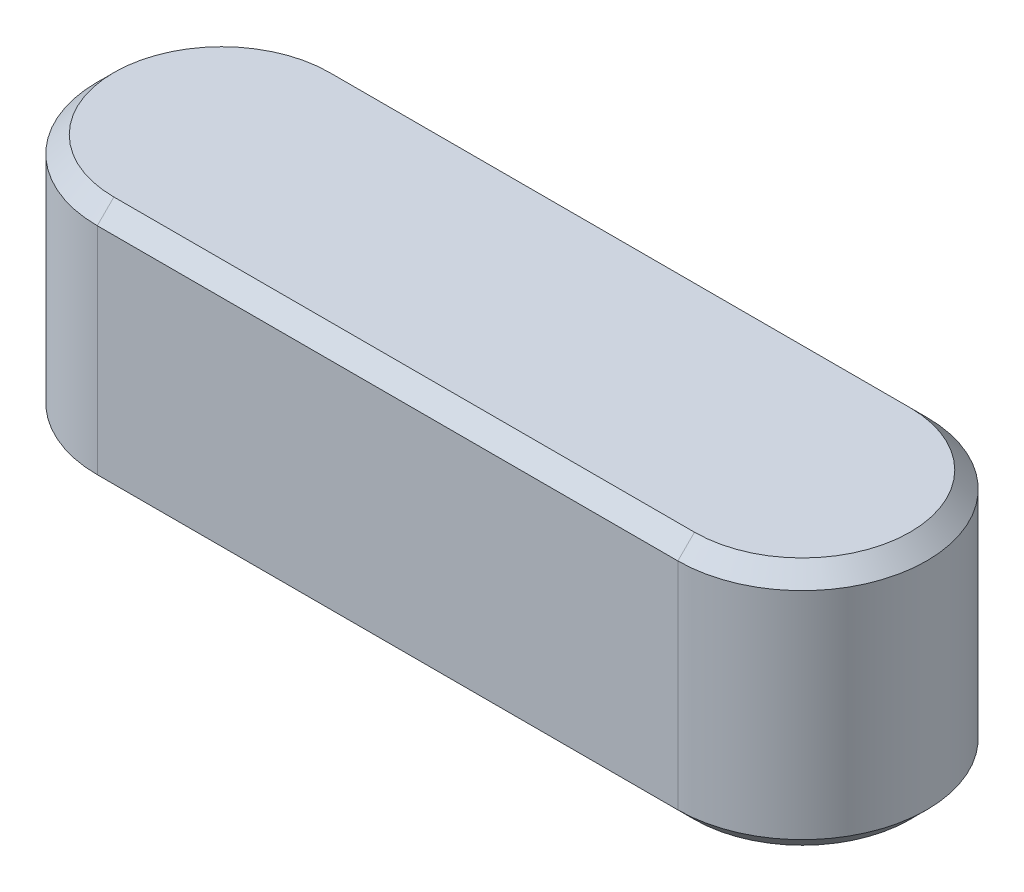
SolidWorks part; units mm, degrees
material "S45C"
ref_plane "Front Plane" through (0, 0, 0) normal (0, 0, 1) x (1, 0, 0)
ref_plane "Top Plane" through (0, 0, 0) normal (0, 1, 0) x (1, 0, 0)
ref_plane "Right Plane" through (0, 0, 0) normal (1, 0, 0) x (0, 0, -1)
sketch "Sketch1" plane through (0, 0, 0) normal (0, 1, 0) x (1, 0, 0)
  line L0 (-5, 0) -> (5, 0) construction
  line L1 (0, 1.5) -> (0, -1.5) construction
  line L3 (-5, 1.5) -> (5, 1.5)
  line L4 (-5, 1.5) -> (-5, -1.5)
  line L5 (-5, -1.5) -> (5, -1.5)
  line L6 (5, 1.5) -> (5, -1.5)
  dimension "L" = 10
  dimension "B" = 3
extrude "Boss-Extrude1" add sketch "Sketch1" along normal blind 3
chamfer "Chamfer1" [suppressed] distance 0.2 angle 45
fillet "Fillet1" 2 edges at (-5, 1.5, 1.5) (-5, 1.5, -1.5) type full round first side face at (0, 1.5, 1.5) second side face at (0, 1.5, -1.5) middle face at (-5, 1.5, 0)
fillet "Fillet2" 2 edges at (5, 1.5, 1.5) (5, 1.5, -1.5) type full round first side face at (0.75, 1.5, 1.5) second side face at (0.75, 1.5, -1.5) middle face at (5, 1.5, 0)
chamfer "Chamfer2" distance 0.2 angle 45 8 edges at (0, 0, -1.5) (-5, 0, 0) (5, 0, 0) (0, 0, 1.5) (0, 3, -1.5) (-5, 3, 0) (5, 3, 0) (0, 3, 1.5)
